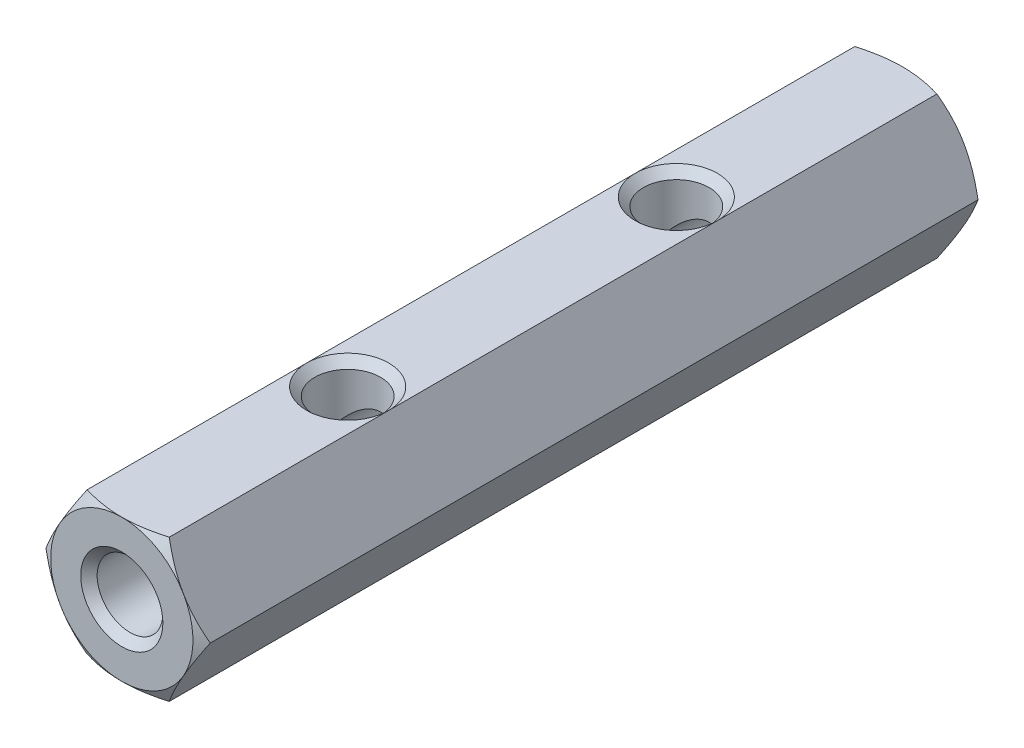
SolidWorks part; units mm, degrees
ref_plane "前视基准面" through (0, 0, 0) normal (0, 0, 1) x (1, 0, 0)
ref_plane "上视基准面" through (0, 0, 0) normal (0, 1, 0) x (1, 0, 0)
ref_plane "右视基准面" through (0, 0, 0) normal (1, 0, 0) x (0, 0, -1)
sketch "草图1" plane through (0, 0, 0) normal (0, 0, 1) x (1, 0, 0)
  line L0 (0, 0) -> (1958.9043, 0) construction
  line L1 (2, 0) -> (1, 1.7321)
  line L2 (1, 1.7321) -> (-1, 1.7321)
  line L3 (-1, 1.7321) -> (-2, 0)
  line L4 (-2, 0) -> (-1, -1.7321)
  line L5 (-1, -1.7321) -> (1, -1.7321)
  line L6 (1, -1.7321) -> (2, 0)
  line L7 (0, 0) -> (0, 1958.9043) construction
  circle A0 centre (0, 0) radius 1.7321 construction
  point P1 (0, 0)
  dimension "D1" = 4
extrude "凸台-拉伸1" add sketch "草图1" along normal mid plane 19
sketch "草图2" plane through (0, 0, 9.5) normal (0, 0, 1) x (1, 0, 0)
  circle A0 centre (0, 0) radius 1.7321
extrude "切除-拉伸1" cut sketch "草图2" against normal through all draft 60 flip side to cut
hole_wizard "M2 螺纹孔1" positions "草图5" profile "草图4" tap size "M2" standard "GB" end condition through all
sketch "草图5" plane through (0, 0, 9.5) normal (0, 0, 1) x (1, 0, 0)
  point P0 (0, 0)
sketch "草图4" plane through (0, 0, 9.5) normal (1, 0, 0) x (0, -1, 0)
  line L0 (0, 0) -> (0, 19)
  line L1 (0, 19) -> (0.8, 19)
  line L2 (0.8, 19) -> (0.8, 0)
  line L5 (0.8, 0) -> (0, 0)
  line L11 (0, -6.35) -> (0, 107.95) construction
  dimension "通孔螺纹孔钻头直径" = 1.6
  dimension "通孔螺纹孔钻头深度" = 19
cosmetic thread "孔螺蚊线1"
hole_wizard "M2 螺纹孔2" positions "草图6" profile "草图7" tap size "M2" standard "GB" end condition through all
sketch "草图6" plane through (0, 1.7321, 0) normal (0, 1, 0) x (1, 0, 0)
  point P0 (0, -4)
  dimension "D1" = 4
sketch "草图7" plane through (0, 1.7321, 4) normal (1, 0, 0) x (0, 0, 1)
  line L0 (0, 0) -> (0, 3.4641)
  line L1 (0, 3.4641) -> (0.8, 3.4641)
  line L2 (0.8, 3.4641) -> (0.8, 0)
  line L5 (0.8, 0) -> (0, 0)
  line L11 (0, -6.35) -> (0, 107.95) construction
  dimension "通孔螺纹孔钻头直径" = 1.6
  dimension "通孔螺纹孔钻头深度" = 3.4641
cosmetic thread "孔螺蚊线3"
mirror "镜向1" about plane through (0, 0, 0) normal (0, 0, 1) of "M2 螺纹孔1", "M2 螺纹孔2", "切除-拉伸1"
cosmetic thread "孔螺蚊线4"
chamfer "倒角1" distance 0.2 angle 45 6 edges at (0, -1.7321, 4.8) (0.8, 0, 9.5) (0, 1.7321, 4.8) (0, 1.7321, -3.2) (0.8, 0, -9.5) (0, -1.7321, -3.2)
